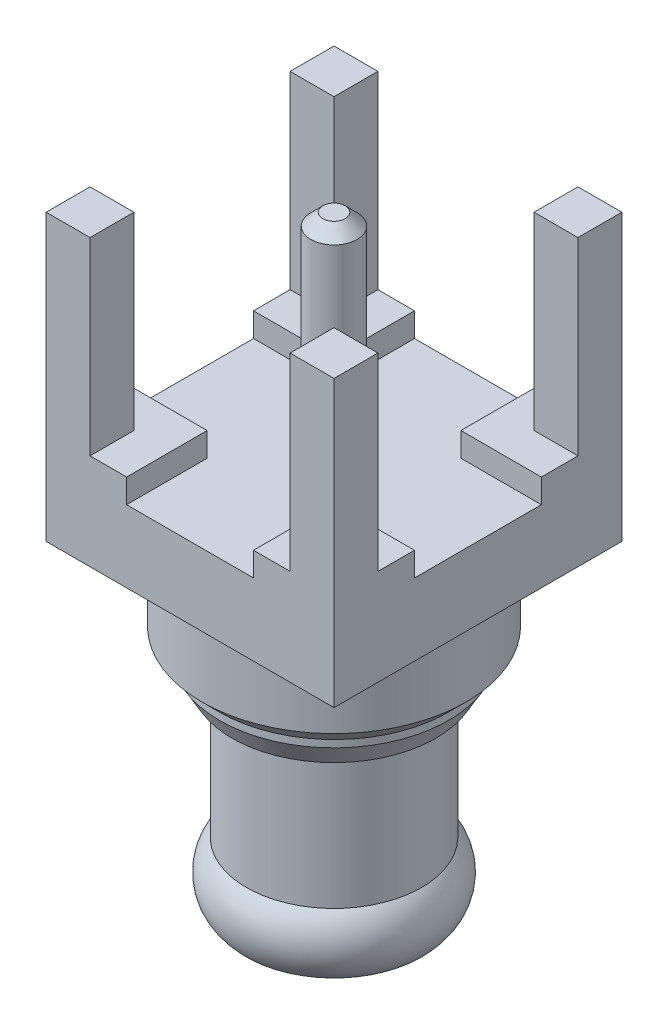
SolidWorks part; units mm, degrees
ref_plane "Front Plane" through (0, 0, 0) normal (0, 0, 1) x (1, 0, 0)
ref_plane "Top Plane" through (0, 0, 0) normal (0, 1, 0) x (1, 0, 0)
ref_plane "Right Plane" through (0, 0, 0) normal (1, 0, 0) x (0, 0, -1)
sketch "Sketch1" plane through (0, 0, 0) normal (0, 1, 0) x (1, 0, 0)
  line L1 (-2.9972, -2.9972) -> (2.9972, -2.9972)
  line L2 (-2.9972, -2.9972) -> (-2.9972, 2.9972)
  line L3 (-2.9972, 2.9972) -> (2.9972, 2.9972)
  line L4 (2.9972, -2.9972) -> (2.9972, 2.9972)
  line L5 (-2.9972, -2.9972) -> (2.9972, 2.9972) construction
  line L6 (-2.9972, 2.9972) -> (2.9972, -2.9972) construction
  point P0 (0, 0)
  dimension "D1" = 5.9944
extrude "Boss-Extrude1" add sketch "Sketch1" along normal blind 1.5
sketch "Sketch2" plane through (0, 1.5, 0) normal (0, 1, 0) x (1, 0, 0)
  line L1 (-2.9972, 2.9972) -> (-1.3208, 2.9972)
  line L2 (-2.9972, 2.9972) -> (-2.9972, 1.3208)
  line L3 (-2.9972, 1.3208) -> (-1.3208, 1.3208)
  line L4 (-1.3208, 2.9972) -> (-1.3208, 1.3208)
  line L5 (2.9972, 2.9972) -> (1.3208, 2.9972)
  line L6 (2.9972, 2.9972) -> (2.9972, 1.3208)
  line L7 (2.9972, 1.3208) -> (1.3208, 1.3208)
  line L8 (1.3208, 2.9972) -> (1.3208, 1.3208)
  line L9 (2.9972, -2.9972) -> (1.3208, -2.9972)
  line L10 (2.9972, -2.9972) -> (2.9972, -1.3208)
  line L11 (2.9972, -1.3208) -> (1.3208, -1.3208)
  line L12 (1.3208, -2.9972) -> (1.3208, -1.3208)
  line L13 (-2.9972, -2.9972) -> (-1.3208, -2.9972)
  line L14 (-2.9972, -2.9972) -> (-2.9972, -1.3208)
  line L15 (-2.9972, -1.3208) -> (-1.3208, -1.3208)
  line L16 (-1.3208, -2.9972) -> (-1.3208, -1.3208)
  dimension "D1" = 2.6416
extrude "Boss-Extrude2" add sketch "Sketch2" along normal blind 0.5
sketch "Sketch3" plane through (0, 2, 0) normal (0, 1, 0) x (1, 0, 0)
  line L1 (-2.0828, -2.0828) -> (-2.9972, -2.0828)
  line L2 (-2.0828, -2.0828) -> (-2.0828, -2.9972)
  line L3 (-2.0828, -2.9972) -> (-2.9972, -2.9972)
  line L4 (-2.9972, -2.0828) -> (-2.9972, -2.9972)
  line L5 (2.0828, -2.0828) -> (2.9972, -2.0828)
  line L6 (2.0828, -2.0828) -> (2.0828, -2.9972)
  line L7 (2.0828, -2.9972) -> (2.9972, -2.9972)
  line L8 (2.9972, -2.0828) -> (2.9972, -2.9972)
  line L9 (2.0828, 2.0828) -> (2.9972, 2.0828)
  line L10 (2.0828, 2.0828) -> (2.0828, 2.9972)
  line L11 (2.0828, 2.9972) -> (2.9972, 2.9972)
  line L12 (2.9972, 2.0828) -> (2.9972, 2.9972)
  line L13 (-2.0828, 2.0828) -> (-2.9972, 2.0828)
  line L14 (-2.0828, 2.0828) -> (-2.0828, 2.9972)
  line L15 (-2.0828, 2.9972) -> (-2.9972, 2.9972)
  line L16 (-2.9972, 2.0828) -> (-2.9972, 2.9972)
  dimension "D1" = 0.9144
extrude "Boss-Extrude3" add sketch "Sketch3" along normal blind 3.937
sketch "Sketch4" plane through (0, 0, 0) normal (0, -1, 0) x (1, 0, 0)
  line L3 (0, -2.7472) -> (1.4469, -2.7472) construction
  line L4 (2.9972, -2.9972) -> (-2.9972, -2.9972) construction
  circle A0 centre (0, 0) radius 2.7472
  circle A1 centre (0, 0) radius 1.3208
  dimension "D1" = 0.25
  dimension "D2" = 2.6416
extrude "Boss-Extrude4" add sketch "Sketch4" along normal offset from surface (6.5852 mm away) 8.5852 up to face at (2.1336, 2, -2.1336)
chamfer "Chamfer1" distance 0.125 angle 45 2 edges at (0, -6.5852, -1.3208) (0, -6.5852, -2.7472)
sketch "Sketch5" plane through (0, 0, 0) normal (0, 0, 1) x (1, 0, 0)
  line L0 (-2.7472, 0) -> (-2.7472, -1.524)
  line L1 (-2.0828, 5.937) -> (-2.0828, 2) construction
  line L2 (-2.9972, 0) -> (2.9972, 0) construction
  line L3 (-2.7472, 0) -> (-2.7472, -6.4602) construction
  line L4 (-2.7472, -1.524) -> (-2.3828, -1.8884)
  line L5 (-2.3828, -1.8884) -> (-2.3828, -2.0384)
  line L6 (2.7472, -3.2301) -> (-2.7472, -3.2301) construction
  line L7 (2.7472, -6.4602) -> (2.7472, 0) construction
  line L8 (-2.3828, -2.0384) -> (-2.123, -2.4884)
  line L9 (-1.823, -5.3307) -> (-1.1958, -5.958) construction
  line L10 (-2.123, -2.4884) -> (-1.823, -2.4884)
  line L11 (-2.6222, -6.5852) -> (2.6222, -6.5852) construction
  line L12 (-1.823, -2.4884) -> (-1.823, -5.3307)
  line L13 (-1.1958, -5.958) -> (-1.823, -6.5852) construction
  line L14 (-1.823, -6.5852) -> (-3.1931, -6.5852)
  line L15 (-3.1931, -6.5852) -> (-3.1931, 0)
  line L16 (-3.1931, 0) -> (-2.7472, 0)
  arc A0 (-1.823, -5.3307) -> (-1.823, -6.5852) centre (-1.1958, -5.958) ccw
  dimension "D1" = 45
  dimension "D2" = 0.15
  dimension "D3" = 30
  dimension "D4" = 0.3
  dimension "D5" = 0.45
  dimension "D6" = 0.3
  dimension "D7" = 1.524
ref_axis "Axis1" through (0, -6.4602, 0) along (0, 1, 0)
revolve "Cut-Revolve1" cut sketch "Sketch5" angle 360 about axis through (0, -6.4602, 0) along (0, 1, 0)
sketch "Sketch7" plane through (0, 1.5, 0) normal (0, 1, 0) x (1, 0, 0)
  circle A0 centre (0, 0) radius 0.4826
  dimension "D1" = 0.9652
extrude "Boss-Extrude5" add sketch "Sketch7" along normal up to surface (4.437 mm away) up to face at (2.54, 5.937, -2.54)
chamfer "Chamfer2" distance 0.25 angle 45 1 edges at (0, 5.937, -0.4826)
sketch "Sketch8" plane through (0, 5.937, 0) normal (0, 1, 0) x (1, 0, 0)
  line L0 (2.54, -2.0828) -> (2.54, -2.9972) construction
  line L1 (2.9972, -2.0828) -> (2.0828, -2.0828) construction
  line L2 (2.0828, -2.9972) -> (2.9972, -2.9972) construction
  line L3 (-2.0828, 2.54) -> (-2.9972, 2.54) construction
  line L4 (-2.0828, 2.0828) -> (-2.0828, 2.9972) construction
  line L5 (-2.9972, 2.9972) -> (-2.9972, 2.0828) construction
  point P12 (-2.54, 2.54)
  point P13 (2.54, -2.54)
ref_axis "Axis2" through (2.54, 5.937, 2.54) along (0, -1, 0)
ref_axis "Axis3" through (-2.54, 5.937, -2.54) along (0, -1, 0)
